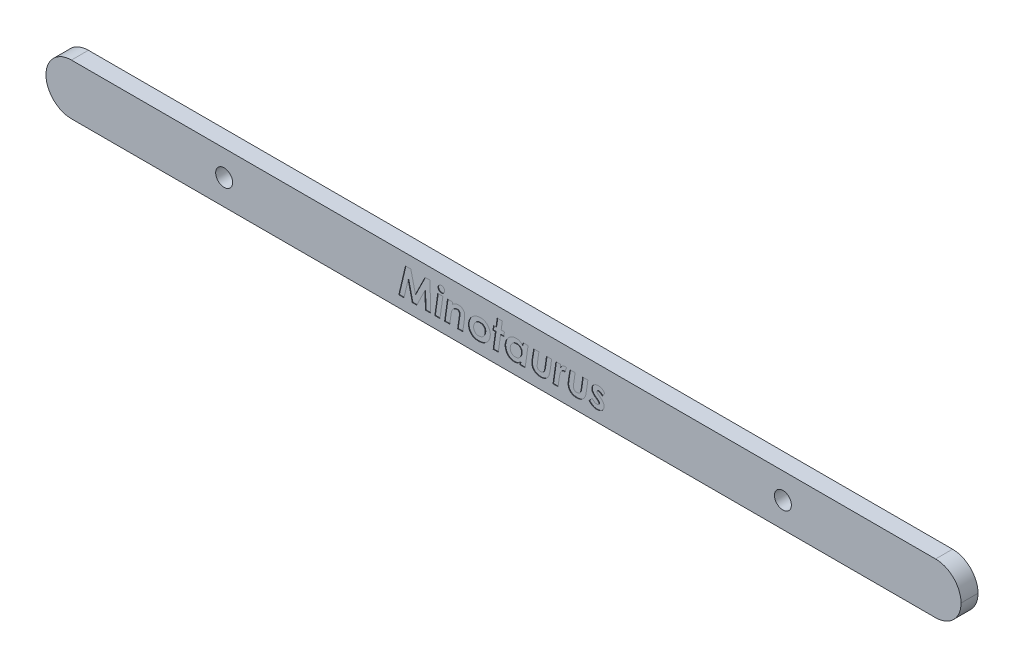
SolidWorks part; units mm, degrees
material "Acrylic (Medium-high impact)"
ref_plane "Front Plane" through (0, 0, 0) normal (0, 0, 1) x (1, 0, 0)
ref_plane "Top Plane" through (0, 0, 0) normal (0, 1, 0) x (1, 0, 0)
ref_plane "Right Plane" through (0, 0, 0) normal (1, 0, 0) x (0, 0, -1)
sketch "Sketch1" plane through (0, 0, 0) normal (0, 0, 1) x (1, 0, 0)
  line L0 (0, -1.65) -> (0, 1.65) construction
  line L1 (-80.9, 4.5) -> (80.9, 4.5)
  line L2 (-80.9, 4.5) -> (-80.9, -4.5)
  line L3 (-80.9, -4.5) -> (80.9, -4.5)
  line L4 (80.9, 4.5) -> (80.9, -4.5)
  circle A0 centre (-49.4, 0) radius 1.5
  circle A1 centre (49.4, 0) radius 1.5
  point P4 (0, 4.5)
  point P6 (-80.9, 0)
  dimension "D3" = 3
  dimension "D4" = 30
  dimension "D2" = 98.8
  dimension "D5" = 3
  dimension "D1" = 9
extrude "Boss-Extrude1" add sketch "Sketch1" along normal mid plane 3
sketch "Sketch2" plane through (0, 0, 1.5) normal (0, 0, 1) x (1, 0, 0)
  line L0 (-35.6678, -2.5) -> (35.6678, -2.5) construction
  line L2 (-80.9, -4.5) -> (80.9, -4.5) construction
  text T0 "<b><i>Minotaurus</i></b>" font "Century Gothic" height 5
  point P5 (0, 0)
  point P7 (0, -2.5)
  dimension "D1" = 2
extrude "Cut-Extrude1" cut sketch "Sketch2" against normal blind 0.1
fillet "Fillet1" radius 4.5 4 edges at (80.9, -4.5, 0) (80.9, 4.5, 0) (-80.9, -4.5, 0) (-80.9, 4.5, 0)
